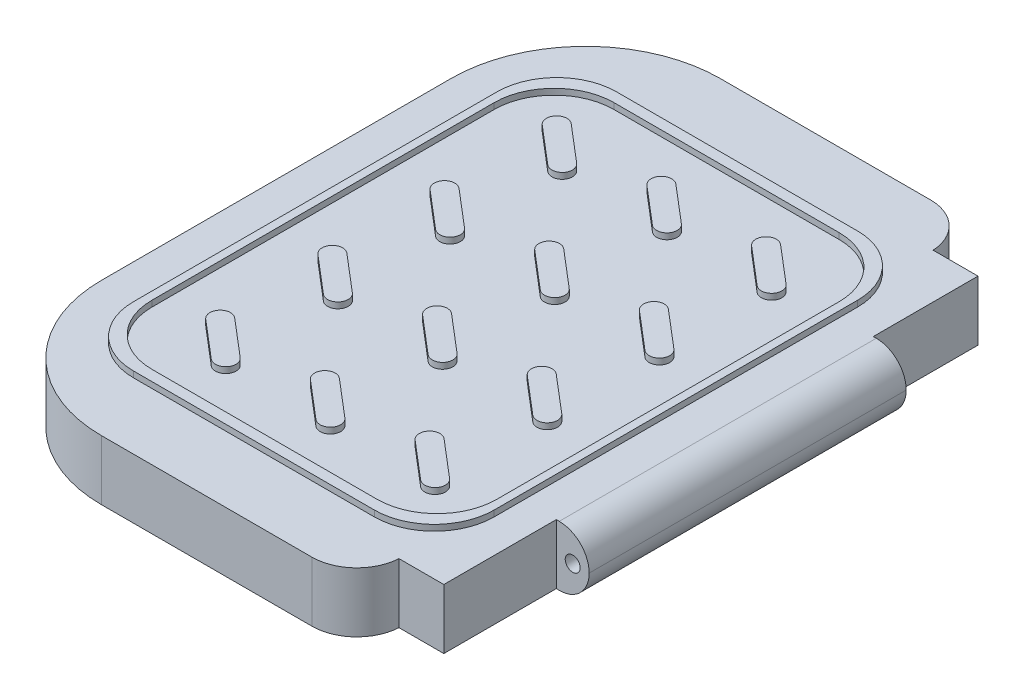
SolidWorks part; units mm, degrees
ref_plane "Front Plane" through (0, 0, 0) normal (0, 0, 1) x (1, 0, 0)
ref_plane "Top Plane" through (0, 0, 0) normal (0, 1, 0) x (1, 0, 0)
ref_plane "Right Plane" through (0, 0, 0) normal (1, 0, 0) x (0, 0, -1)
sketch "Sketch1" plane through (0, 0, 0) normal (0, 1, 0) x (1, 0, 0)
  line L0 (0, 108.5909) -> (0, -103.4091)
  line L1 (0, 108.5909) -> (-22, 108.5909)
  line L2 (0, -103.4091) -> (-22, -103.4091)
  line L3 (-22, 108.5909) -> (-22, 178.5909)
  line L4 (-22, -103.4091) -> (-22, -173.4091)
  line L5 (-22, 178.5909) -> (-51.9973, 178.5909)
  line L6 (-51.9973, 178.5909) -> (-51.9973, 206.8399)
  line L7 (-51.9973, 206.8399) -> (-312.6118, 206.8399)
  line L8 (-312.6118, 206.8399) -> (-312.6118, -206.8399)
  line L9 (0, 0) -> (-51.9973, 0) construction
  line L10 (-22, -108.5909) -> (-22, -178.5909)
  line L11 (-22, -178.5909) -> (-51.9973, -178.5909)
  line L12 (-51.9973, -178.5909) -> (-51.9973, -206.8399)
  line L13 (-51.9973, -206.8399) -> (-312.6118, -206.8399)
  point P18 (-312.6118, 0)
  dimension "D1" = 212
  dimension "D2" = 22
  dimension "D3" = 22
  dimension "D4" = 70
  dimension "D5" = 70
extrude "Boss-Extrude1" add sketch "Sketch1" along normal blind 40 contours L13 L12 L11 L10 L4 L2 L0 L1 L3 L5 L6 L7 L8 region at (-163.1808, 0, -0.0981)
sketch "Sketch2" plane through (0, 0, 103.4091) normal (0, 0, 1) x (1, 0, 0)
  circle A0 centre (-11, 20) radius 5
  dimension "D1" = 10
extrude "Cut-Extrude1" cut sketch "Sketch2" against normal mid plane 660
fillet "Fillet1" radius 90 2 edges at (-312.6118, 20, -206.8399) (-312.6118, 20, 206.8399)
fillet "Fillet2" radius 30 2 edges at (-51.9973, 20, -206.8399) (-51.9973, 20, 206.8399)
shell "Shell4" thickness 10 removed face at (-103.7423, 0, -0.7403)
sketch "Sketch4" plane through (0, 40, 0) normal (0, 1, 0) x (1, 0, 0)
  line L1 (-84.305, 160.4513) -> (-245.523, 160.4513)
  line L2 (-44.305, 120.4513) -> (-44.305, -122.6727)
  line L3 (-84.305, -162.6727) -> (-245.523, -162.6727)
  line L4 (-285.523, 120.4513) -> (-285.523, -122.6727)
  line L5 (-44.305, 160.4513) -> (-285.523, -162.6727) construction
  line L6 (-44.305, -162.6727) -> (-285.523, 160.4513) construction
  line L7 (-89.6097, 153.3453) -> (-240.2182, 153.3453)
  line L8 (-49.6097, 113.3453) -> (-49.6097, -115.5668)
  line L9 (-89.6097, -155.5668) -> (-240.2182, -155.5668)
  line L10 (-280.2182, 113.3453) -> (-280.2182, -115.5668)
  line L11 (-49.6097, 153.3453) -> (-280.2182, -155.5668) construction
  line L12 (-49.6097, -155.5668) -> (-280.2182, 153.3453) construction
  arc A0 (-84.305, 160.4513) -> (-44.305, 120.4513) centre (-84.305, 120.4513) cw
  arc A1 (-44.305, -122.6727) -> (-84.305, -162.6727) centre (-84.305, -122.6727) cw
  arc A2 (-245.523, -162.6727) -> (-285.523, -122.6727) centre (-245.523, -122.6727) cw
  arc A3 (-245.523, 160.4513) -> (-285.523, 120.4513) centre (-245.523, 120.4513) ccw
  arc A4 (-240.2182, -155.5668) -> (-280.2182, -115.5668) centre (-240.2182, -115.5668) cw
  arc A5 (-49.6097, -115.5668) -> (-89.6097, -155.5668) centre (-89.6097, -115.5668) cw
  arc A6 (-89.6097, 153.3453) -> (-49.6097, 113.3453) centre (-89.6097, 113.3453) cw
  arc A7 (-240.2182, 153.3453) -> (-280.2182, 113.3453) centre (-240.2182, 113.3453) ccw
  point P0 (-164.914, -1.1107)
  point P17 (-164.914, -1.1107)
  dimension "D1" = 40
  dimension "D2" = 40
extrude "Boss-Extrude2" add sketch "Sketch4" along normal blind 4
sketch "Sketch5" plane through (0, 40, 0) normal (0, 1, 0) x (1, 0, 0)
  line L0 (-221.882, 100.4693) -> (-246.786, 121.6749) construction
  line L1 (-226.3339, 95.2409) -> (-251.2379, 116.4465)
  line L2 (-217.4301, 105.6977) -> (-242.3341, 126.9032)
  line L3 (-151.882, 100.4693) -> (-176.786, 121.6749) construction
  line L4 (-156.3339, 95.2409) -> (-181.2379, 116.4465)
  line L5 (-147.4301, 105.6977) -> (-172.3341, 126.9032)
  line L6 (-81.882, 100.4693) -> (-106.786, 121.6749) construction
  line L7 (-86.3339, 95.2409) -> (-111.2379, 116.4465)
  line L8 (-77.4301, 105.6977) -> (-102.3341, 126.9032)
  line L9 (-151.882, 25.4693) -> (-176.786, 46.6749) construction
  line L10 (-156.3339, 20.2409) -> (-181.2379, 41.4465)
  line L11 (-147.4301, 30.6977) -> (-172.3341, 51.9032)
  line L12 (-81.882, 25.4693) -> (-106.786, 46.6749) construction
  line L13 (-86.3339, 20.2409) -> (-111.2379, 41.4465)
  line L14 (-77.4301, 30.6977) -> (-102.3341, 51.9032)
  line L15 (-151.882, -49.5307) -> (-176.786, -28.3251) construction
  line L16 (-156.3339, -54.7591) -> (-181.2379, -33.5535)
  line L17 (-147.4301, -44.3023) -> (-172.3341, -23.0968)
  line L18 (-81.882, -49.5307) -> (-106.786, -28.3251) construction
  line L19 (-86.3339, -54.7591) -> (-111.2379, -33.5535)
  line L20 (-77.4301, -44.3023) -> (-102.3341, -23.0968)
  line L21 (-151.882, -124.5307) -> (-176.786, -103.3251) construction
  line L22 (-156.3339, -129.7591) -> (-181.2379, -108.5535)
  line L23 (-147.4301, -119.3023) -> (-172.3341, -98.0968)
  line L24 (-81.882, -124.5307) -> (-106.786, -103.3251) construction
  line L25 (-86.3339, -129.7591) -> (-111.2379, -108.5535)
  line L26 (-77.4301, -119.3023) -> (-102.3341, -98.0968)
  line L27 (-221.882, 25.4693) -> (-246.786, 46.6749) construction
  line L28 (-226.3339, 20.2409) -> (-251.2379, 41.4465)
  line L29 (-217.4301, 30.6977) -> (-242.3341, 51.9032)
  line L30 (-221.882, -49.5307) -> (-246.786, -28.3251) construction
  line L31 (-226.3339, -54.7591) -> (-251.2379, -33.5535)
  line L32 (-217.4301, -44.3023) -> (-242.3341, -23.0968)
  line L33 (-221.882, -124.5307) -> (-246.786, -103.3251) construction
  line L34 (-226.3339, -129.7591) -> (-251.2379, -108.5535)
  line L35 (-217.4301, -119.3023) -> (-242.3341, -98.0968)
  arc A0 (-226.3339, 95.2409) -> (-217.4301, 105.6977) centre (-221.882, 100.4693) ccw
  arc A1 (-242.3341, 126.9032) -> (-251.2379, 116.4465) centre (-246.786, 121.6749) ccw
  arc A2 (-156.3339, 95.2409) -> (-147.4301, 105.6977) centre (-151.882, 100.4693) ccw
  arc A3 (-172.3341, 126.9032) -> (-181.2379, 116.4465) centre (-176.786, 121.6749) ccw
  arc A4 (-86.3339, 95.2409) -> (-77.4301, 105.6977) centre (-81.882, 100.4693) ccw
  arc A5 (-102.3341, 126.9032) -> (-111.2379, 116.4465) centre (-106.786, 121.6749) ccw
  arc A6 (-156.3339, 20.2409) -> (-147.4301, 30.6977) centre (-151.882, 25.4693) ccw
  arc A7 (-172.3341, 51.9032) -> (-181.2379, 41.4465) centre (-176.786, 46.6749) ccw
  arc A8 (-86.3339, 20.2409) -> (-77.4301, 30.6977) centre (-81.882, 25.4693) ccw
  arc A9 (-102.3341, 51.9032) -> (-111.2379, 41.4465) centre (-106.786, 46.6749) ccw
  arc A10 (-156.3339, -54.7591) -> (-147.4301, -44.3023) centre (-151.882, -49.5307) ccw
  arc A11 (-172.3341, -23.0968) -> (-181.2379, -33.5535) centre (-176.786, -28.3251) ccw
  arc A12 (-86.3339, -54.7591) -> (-77.4301, -44.3023) centre (-81.882, -49.5307) ccw
  arc A13 (-102.3341, -23.0968) -> (-111.2379, -33.5535) centre (-106.786, -28.3251) ccw
  arc A14 (-156.3339, -129.7591) -> (-147.4301, -119.3023) centre (-151.882, -124.5307) ccw
  arc A15 (-172.3341, -98.0968) -> (-181.2379, -108.5535) centre (-176.786, -103.3251) ccw
  arc A16 (-86.3339, -129.7591) -> (-77.4301, -119.3023) centre (-81.882, -124.5307) ccw
  arc A17 (-102.3341, -98.0968) -> (-111.2379, -108.5535) centre (-106.786, -103.3251) ccw
  arc A18 (-226.3339, 20.2409) -> (-217.4301, 30.6977) centre (-221.882, 25.4693) ccw
  arc A19 (-242.3341, 51.9032) -> (-251.2379, 41.4465) centre (-246.786, 46.6749) ccw
  arc A20 (-226.3339, -54.7591) -> (-217.4301, -44.3023) centre (-221.882, -49.5307) ccw
  arc A21 (-242.3341, -23.0968) -> (-251.2379, -33.5535) centre (-246.786, -28.3251) ccw
  arc A22 (-226.3339, -129.7591) -> (-217.4301, -119.3023) centre (-221.882, -124.5307) ccw
  arc A23 (-242.3341, -98.0968) -> (-251.2379, -108.5535) centre (-246.786, -103.3251) ccw
  point P2 (-234.334, 111.0721)
  point P12 (-164.334, 111.0721)
  point P19 (-94.334, 111.0721)
  point P26 (-164.334, 36.0721)
  point P33 (-94.334, 36.0721)
  point P40 (-164.334, -38.9279)
  point P47 (-94.334, -38.9279)
  point P54 (-164.334, -113.9279)
  point P61 (-94.334, -113.9279)
  point P68 (-234.334, 36.0721)
  point P75 (-234.334, -38.9279)
  point P82 (-234.334, -113.9279)
  dimension "D1" = 3
  dimension "D2" = 4
extrude "Boss-Extrude3" add sketch "Sketch5" along normal blind 4
fillet "Fillet4" radius 20 2 edges at (0, 0, -2.5909) (0, 40, -2.5909)
